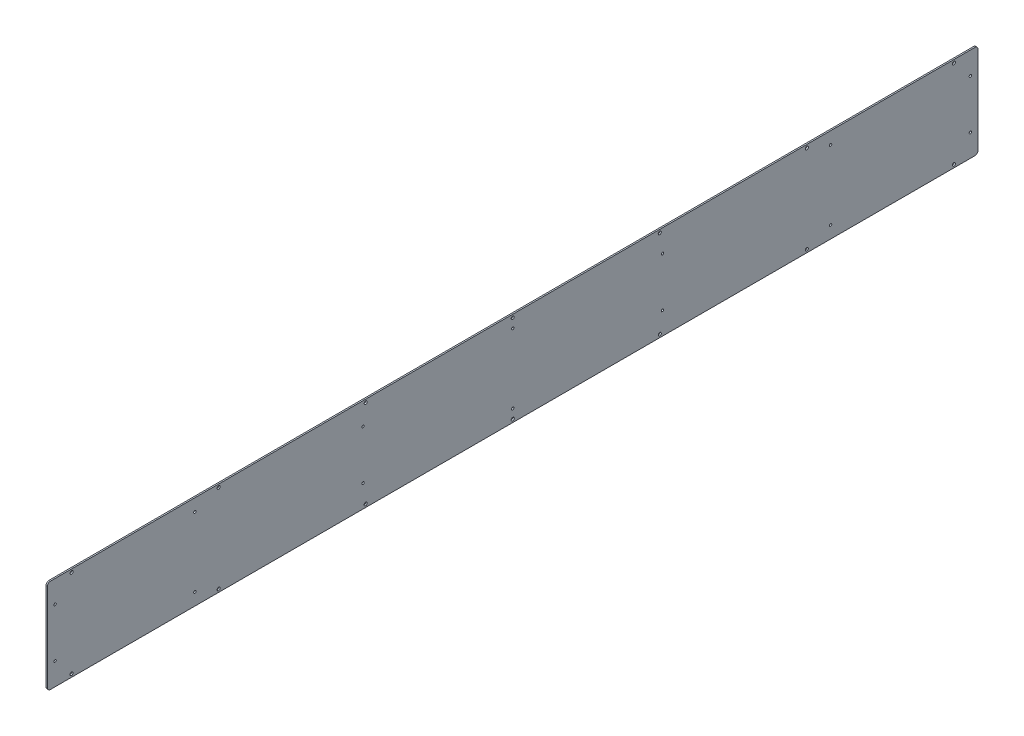
SolidWorks part; units mm, degrees
material "PC High Viscosity"
ref_plane "Front Plane" through (0, 0, 0) normal (0, 0, 1) x (1, 0, 0)
ref_plane "Top Plane" through (0, 0, 0) normal (0, 1, 0) x (1, 0, 0)
ref_plane "Right Plane" through (0, 0, 0) normal (1, 0, 0) x (0, 0, -1)
sketch "Sketch1" plane through (0, 0, 0) normal (1, 0, 0) x (0, 0, -1)
  line L1 (0, 0) -> (1928.8125, 0)
  line L2 (0, 0) -> (0, 194.564)
  line L3 (0, 194.564) -> (1928.8125, 194.564)
  line L4 (1928.8125, 0) -> (1928.8125, 194.564)
  dimension "D1" = 1928.8125
  dimension "D2" = 194.564
extrude "Boss-Extrude1" add sketch "Sketch1" along normal blind 2.9972
sketch "Sketch2" plane through (2.9972, 0, 0) normal (1, 0, 0) x (0, 0, -1)
  line L1 (0, 194.564) -> (0, 0) construction
  line L2 (0, 0) -> (1928.8125, 0) construction
  line L3 (964.4062, 169.164) -> (964.4062, 25.4) construction
  circle A0 centre (15.875, 148.082) radius 2.4511
  circle A1 centre (654.05, 148.082) radius 2.4511
  circle A4 centre (305.562, 169.164) radius 2.4511
  circle A5 centre (964.4062, 169.164) radius 2.4511
  circle A7 centre (964.4062, 25.4) radius 2.4511
  circle A9 centre (305.562, 25.4) radius 2.4511
  circle A10 centre (15.875, 46.482) radius 2.4511
  circle A11 centre (654.05, 46.482) radius 2.4511
  circle A14 centre (1623.2505, 25.4) radius 2.4511
  circle A15 centre (1623.2505, 169.164) radius 2.4511
  circle A16 centre (1912.9375, 46.482) radius 2.4511
  circle A17 centre (1912.9375, 148.082) radius 2.4511
  circle A18 centre (1274.7625, 46.482) radius 2.4511
  circle A19 centre (1274.7625, 148.082) radius 2.4511
  circle A20 centre (1623.2505, 169.164) radius 2.4511 [skipped]
  circle A21 centre (1623.2505, 25.4) radius 2.4511 [skipped]
  point P34 (0, 97.282)
  point P35 (964.4062, 0)
  dimension "D2" = 4.9022
  dimension "D4" = 2
  dimension "D6" = 4.9022
  dimension "D3" = 15.875
  dimension "D5" = 305.562
  dimension "D7" = 71.882
  dimension "D10" = 71.882
  dimension "D11" = 50.8
  dimension "D13" = 654.05
  dimension "D14" = 50.8
  dimension "D8" = 3
  dimension "D9" = 2
  dimension "D12" = 2
extrude "Cut-Extrude1" cut sketch "Sketch2" against normal through all
fillet "Fillet1" radius 6.35 4 edges at (1.4986, 0, -1928.8125) (1.4986, 194.564, -1928.8125) (1.4986, 0, 0) (1.4986, 194.564, 0)
hole_wizard "1/4 (0.25) Diameter Hole1" positions "Sketch3" profile "Sketch4" hole size "1/4" standard "ANSI Inch" end condition through all
sketch "Sketch3" plane through (2.9972, 0, 0) normal (1, 0, 0) x (0, 0, -1)
  line L0 (50.0062, 6.35) -> (354.8062, 6.35) construction
  line L1 (354.8062, 6.35) -> (659.6062, 6.35) construction
  line L2 (659.6062, 6.35) -> (964.4062, 6.35) construction
  line L3 (964.4062, 6.35) -> (1269.2063, 6.35) construction
  line L4 (1269.2063, 6.35) -> (1574.0063, 6.35) construction
  line L5 (1574.0063, 6.35) -> (1878.8063, 6.35) construction
  line L7 (964.4062, 0) -> (964.4062, 194.564) construction
  line L8 (6.35, 0) -> (1922.4625, 0) construction
  line L9 (1922.4625, 194.564) -> (6.35, 194.564) construction
  line L11 (0, 97.282) -> (1928.8125, 97.282) construction
  line L12 (0, 188.214) -> (0, 6.35) construction
  line L13 (1928.8125, 6.35) -> (1928.8125, 188.214) construction
  line L14 (1574.0063, 188.214) -> (1878.8063, 188.214) construction
  line L15 (1269.2063, 188.214) -> (1574.0063, 188.214) construction
  line L16 (964.4062, 188.214) -> (1269.2063, 188.214) construction
  line L17 (659.6062, 188.214) -> (964.4062, 188.214) construction
  line L18 (354.8062, 188.214) -> (659.6062, 188.214) construction
  line L19 (50.0062, 188.214) -> (354.8062, 188.214) construction
  point P0 (964.4062, 6.35)
  point P2 (659.6062, 6.35)
  point P4 (354.8062, 6.35)
  point P6 (50.0062, 6.35)
  point P8 (1269.2063, 6.35)
  point P10 (1574.0063, 6.35)
  point P12 (1878.8063, 6.35)
  point P56 (1878.8063, 188.214)
  point P57 (1574.0063, 188.214)
  point P58 (1269.2063, 188.214)
  point P59 (50.0062, 188.214)
  point P60 (354.8062, 188.214)
  point P61 (659.6062, 188.214)
  point P62 (964.4062, 188.214)
  dimension "D1" = 6.35
  dimension "D2" = 304.8
sketch "Sketch4" plane through (2.9972, 6.35, -964.4062) normal (0, 1, 0) x (0, 0, -1)
  line L0 (0, 0) -> (0, 2.9972)
  line L1 (0, 2.9972) -> (3.175, 2.9972)
  line L2 (3.175, 2.9972) -> (3.175, 0)
  line L5 (3.175, 0) -> (0, 0)
  line L11 (0, -6.35) -> (0, 107.95) construction
  dimension "Thru Hole Dia." = 6.35
  dimension "Thru Hole Depth" = 2.9972
